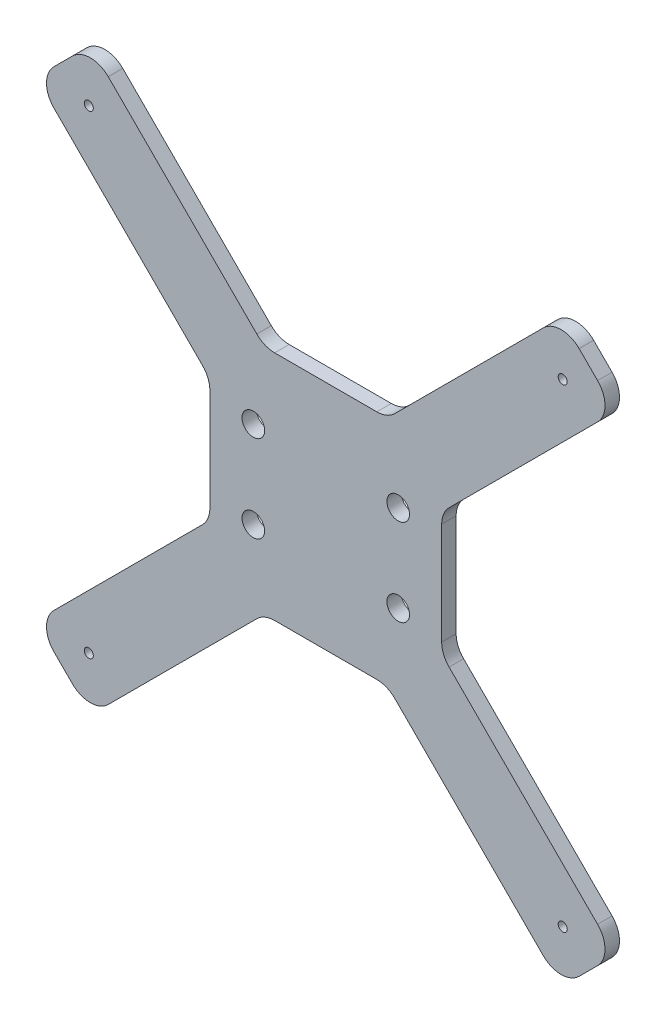
SolidWorks part; units mm, degrees
ref_plane "Front Plane" through (0, 0, 0) normal (0, 0, 1) x (1, 0, 0)
ref_plane "Top Plane" through (0, 0, 0) normal (0, 1, 0) x (1, 0, 0)
ref_plane "Right Plane" through (0, 0, 0) normal (1, 0, 0) x (0, 0, -1)
sketch "Sketch1" plane through (0, 0, 0) normal (0, 0, 1) x (1, 0, 0)
  line L0 (0, 184.15) -> (60.96, 123.19)
  line L5 (19.05, 203.2) -> (80.01, 142.24)
  line L6 (0, 19.05) -> (60.96, 80.01)
  line L7 (19.05, 0) -> (80.01, 60.96)
  line L8 (0, 184.15) -> (19.05, 203.2)
  line L9 (184.15, 203.2) -> (203.2, 184.15)
  line L10 (203.2, 19.05) -> (184.15, 0)
  line L11 (0, 19.05) -> (19.05, 0)
  line L12 (80.01, 142.24) -> (123.19, 142.24)
  line L13 (80.01, 60.96) -> (123.19, 60.96)
  line L14 (60.96, 123.19) -> (60.96, 80.01)
  line L15 (142.24, 123.19) -> (142.24, 80.01)
  line L17 (123.19, 60.96) -> (184.15, 0)
  line L18 (142.24, 80.01) -> (203.2, 19.05)
  line L19 (123.19, 142.24) -> (184.15, 203.2)
  line L20 (142.24, 123.19) -> (203.2, 184.15)
extrude "Boss-Extrude1" add sketch "Sketch1" along normal blind 5.08
fillet "Fillet1" radius 8.89 16 edges at (60.96, 80.01, 2.54) (60.96, 123.19, 2.54) (0, 184.15, 2.54) (19.05, 203.2, 2.54) (80.01, 142.24, 2.54) (123.19, 142.24, 2.54) (184.15, 203.2, 2.54) (203.2, 184.15, 2.54) (142.24, 123.19, 2.54) (142.24, 80.01, 2.54) (203.2, 19.05, 2.54) (184.15, 0, 2.54) (123.19, 60.96, 2.54) (80.01, 60.96, 2.54) (0, 19.05, 2.54) (19.05, 0, 2.54)
sketch "Sketch2" plane through (0, 0, 5.08) normal (0, 0, 1) x (1, 0, 0)
  line L0 (83.6924, 60.96) -> (119.5076, 60.96) construction
  line L1 (119.5076, 142.24) -> (83.6924, 142.24) construction
  line L2 (142.24, 83.6924) -> (142.24, 119.5076) construction
  line L3 (60.96, 119.5076) -> (60.96, 83.6924) construction
  circle A0 centre (127, 86.36) radius 3.9687
  circle A1 centre (127, 116.84) radius 3.9687
  circle A2 centre (76.2, 86.36) radius 3.9687
  circle A3 centre (76.2, 116.84) radius 3.9687
  dimension "D1" = 7.9375
  dimension "D2" = 7.9375
  dimension "D7" = 7.9375
  dimension "D8" = 7.9375
  dimension "D3" = 25.4
  dimension "D4" = 25.4
  dimension "D5" = 15.24
  dimension "D6" = 15.24
  dimension "D9" = 15.24
  dimension "D10" = 15.24
extrude "Cut-Extrude1" cut sketch "Sketch2" against normal through all
sketch "Sketch3" plane through (0, 0, 5.08) normal (0, 0, 1) x (1, 0, 0)
  line L0 (196.9138, 190.4362) -> (190.4362, 196.9138) construction
  line L1 (177.8638, 196.9138) -> (125.7938, 144.8438) construction
  line L4 (12.7638, 196.9138) -> (6.2862, 190.4362) construction
  line L5 (77.4062, 144.8438) -> (25.3362, 196.9138) construction
  line L6 (6.2862, 12.7638) -> (12.7638, 6.2862) construction
  line L7 (25.3362, 6.2862) -> (77.4062, 58.3562) construction
  line L8 (190.4362, 6.2862) -> (196.9138, 12.7638) construction
  line L9 (125.7938, 58.3562) -> (177.8638, 6.2862) construction
  circle A0 centre (184.6888, 184.7007) radius 1.5875
  circle A1 centre (18.5112, 184.7007) radius 1.5875
  circle A2 centre (18.5112, 18.4993) radius 1.5875
  circle A3 centre (184.6888, 18.4993) radius 1.5875
  dimension "D3" = 3.175
  dimension "D6" = 3.175
  dimension "D7" = 3.175
  dimension "D10" = 3.175
  dimension "D1" = 12.7
  dimension "D2" = 13.462
  dimension "D4" = 12.7
  dimension "D5" = 13.462
  dimension "D8" = 12.7
  dimension "D9" = 13.462
  dimension "D11" = 12.7
  dimension "D12" = 13.462
extrude "Cut-Extrude2" cut sketch "Sketch3" against normal through all
